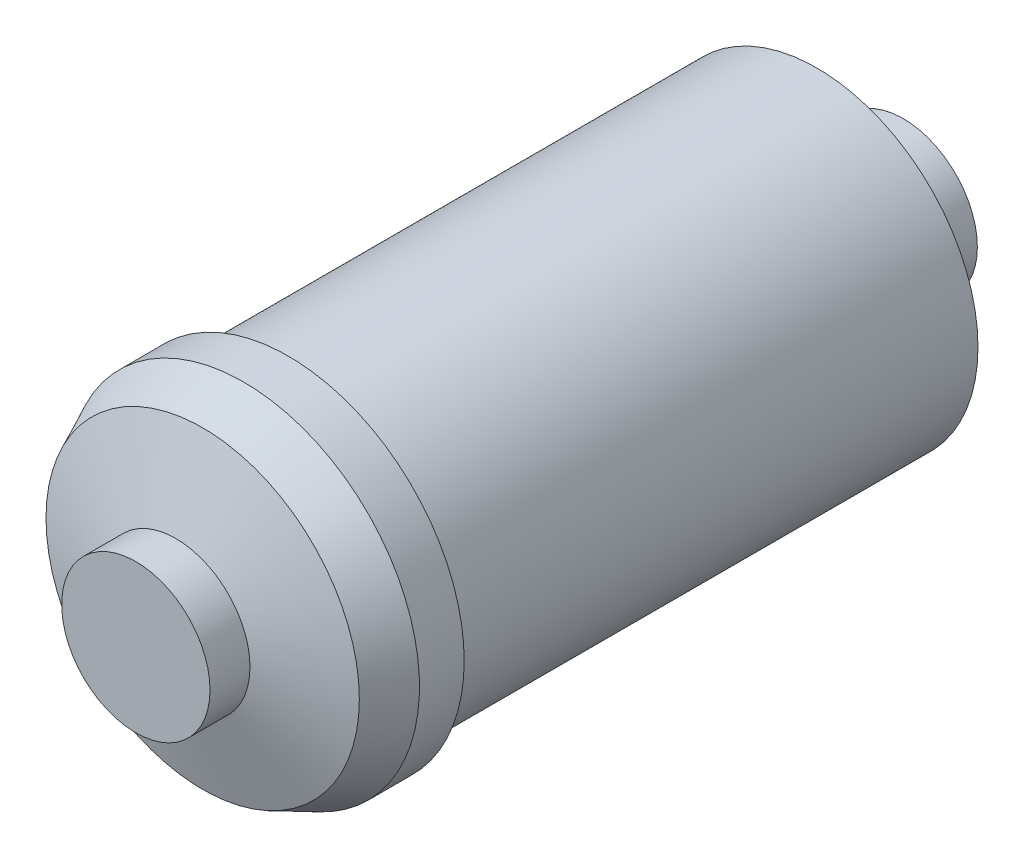
SolidWorks part; units mm, degrees
ref_plane "Front Plane" through (0, 0, 0) normal (0, 0, 1) x (1, 0, 0)
ref_plane "Top Plane" through (0, 0, 0) normal (0, 1, 0) x (1, 0, 0)
ref_plane "Right Plane" through (0, 0, 0) normal (1, 0, 0) x (0, 0, -1)
sketch "Sketch1" plane through (0, 0, 0) normal (0, 0, 1) x (1, 0, 0)
  circle A0 centre (0, 0) radius 14.732
  dimension "D1" = 29.464
extrude "Boss-Extrude1" add sketch "Sketch1" along normal blind 8.255
sketch "Sketch2" plane through (0, 0, 8.255) normal (0, 0, 1) x (1, 0, 0)
  circle A1 centre (0, 0) radius 14.732
  circle A2 centre (0, 0) radius 14.732
  dimension "D1" = 0
ref_plane "Plane1" through (0, 0, 17.145) normal (0, 0, 1) x (1, 0, 0)
sketch "Sketch3" plane through (0, 0, 17.145) normal (0, 0, 1) x (1, 0, 0)
  circle A0 centre (0, 0) radius 32.004
  dimension "D1" = 64.008
loft "Loft1" add profiles "Sketch2", "Sketch3" connector at (0.0833, 14.7318, 8.255) connector at (5.542, 31.5205, 17.145)
sketch "Sketch4" plane through (0, 0, 17.145) normal (0, 0, 1) x (1, 0, 0)
  circle A1 centre (0, 0) radius 32.004
  circle A2 centre (0, 0) radius 32.004
  dimension "D1" = 0
extrude "Boss-Extrude2" add sketch "Sketch4" along normal blind 104.9655
sketch "Sketch5" plane through (0, 0, 122.1105) normal (0, 0, 1) x (1, 0, 0)
  circle A0 centre (0, 0) radius 34.925
  dimension "D1" = 69.85
extrude "Boss-Extrude3" add sketch "Sketch5" along normal blind 8.89
sketch "Sketch6" plane through (0, 0, 131.0005) normal (0, 0, 1) x (1, 0, 0)
  circle A1 centre (0, 0) radius 34.925
  circle A2 centre (0, 0) radius 34.925
  dimension "D1" = 0
ref_plane "Plane2" through (0, 0, 139.1285) normal (0, 0, 1) x (1, 0, 0)
sketch "Sketch7" plane through (0, 0, 139.1285) normal (0, 0, 1) x (1, 0, 0)
  circle A0 centre (0, 0) radius 31.115
  dimension "D1" = 62.23
loft "Loft2" add profiles "Sketch6", "Sketch7" connector at (-0.1975, 34.9244, 131.0005) connector at (2.9087, 30.9787, 139.1285)
sketch "Sketch8" plane through (0, 0, 139.1285) normal (0, 0, 1) x (1, 0, 0)
  circle A1 centre (0, 0) radius 31.115
  circle A2 centre (0, 0) radius 31.115
  dimension "D1" = 0
ref_plane "Plane3" through (0, 0, 144.4625) normal (0, 0, 1) x (1, 0, 0)
sketch "Sketch9" plane through (0, 0, 144.4625) normal (0, 0, 1) x (1, 0, 0)
  circle A0 centre (0, 0) radius 14.732
  dimension "D1" = 29.464
loft "Loft3" add profiles "Sketch8", "Sketch9" connector at (0.8015, 31.1047, 139.1285) connector at (0.4453, 14.7253, 144.4625)
sketch "Sketch10" plane through (0, 0, 144.4625) normal (0, 0, 1) x (1, 0, 0)
  circle A1 centre (0, 0) radius 14.732
  circle A2 centre (0, 0) radius 14.732
  dimension "D1" = 0
extrude "Boss-Extrude4" add sketch "Sketch10" along normal blind 7.9375
